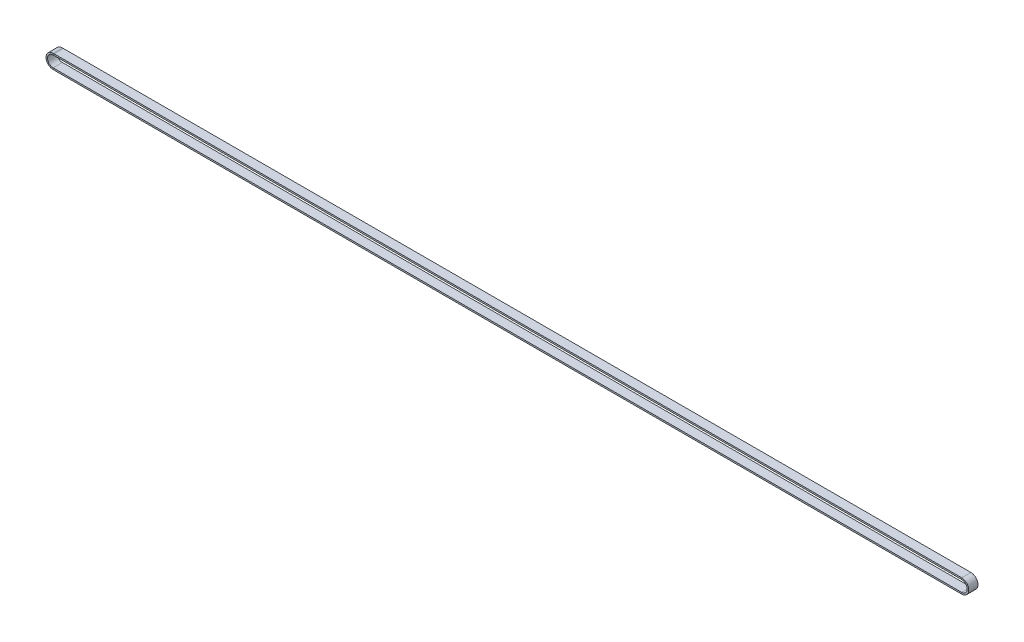
SolidWorks part; units mm, degrees
ref_plane "Front Plane" through (0, 0, 0) normal (0, 0, 1) x (1, 0, 0)
ref_plane "Top Plane" through (0, 0, 0) normal (0, 1, 0) x (1, 0, 0)
ref_plane "Right Plane" through (0, 0, 0) normal (1, 0, 0) x (0, 0, -1)
sketch "Sketch2" plane through (0, 0, 0) normal (0, 0, 1) x (1, 0, 0)
  line L0 (0, 0) -> (1, 0) construction
  line L1 (0, 0) -> (0, 1) construction
  line L2 (-1, -89.604) -> (883.5206, -89.604)
  line L3 (883.5206, -103.404) -> (-1, -103.404)
  arc A0 (-1, -103.404) -> (-1, -89.604) centre (-1, -96.504) cw
  arc A1 (883.5206, -89.604) -> (883.5206, -103.404) centre (883.5206, -96.504) cw
sketch "Sketch3" plane through (0, 0, 0) normal (1, 0, 0) x (0, 0, -1)
  line L1 (0, -91.104) -> (-9, -91.104)
  line L2 (0, -91.104) -> (0, -89.604)
  line L3 (0, -89.604) -> (-9, -89.604)
  line L4 (-9, -91.104) -> (-9, -89.604)
  point P4 (0, -90.6863)
  dimension "D1" = 9
  dimension "D2" = 1.5
sweep "Sweep1" add profiles "Sketch3" path "Sketch2"
